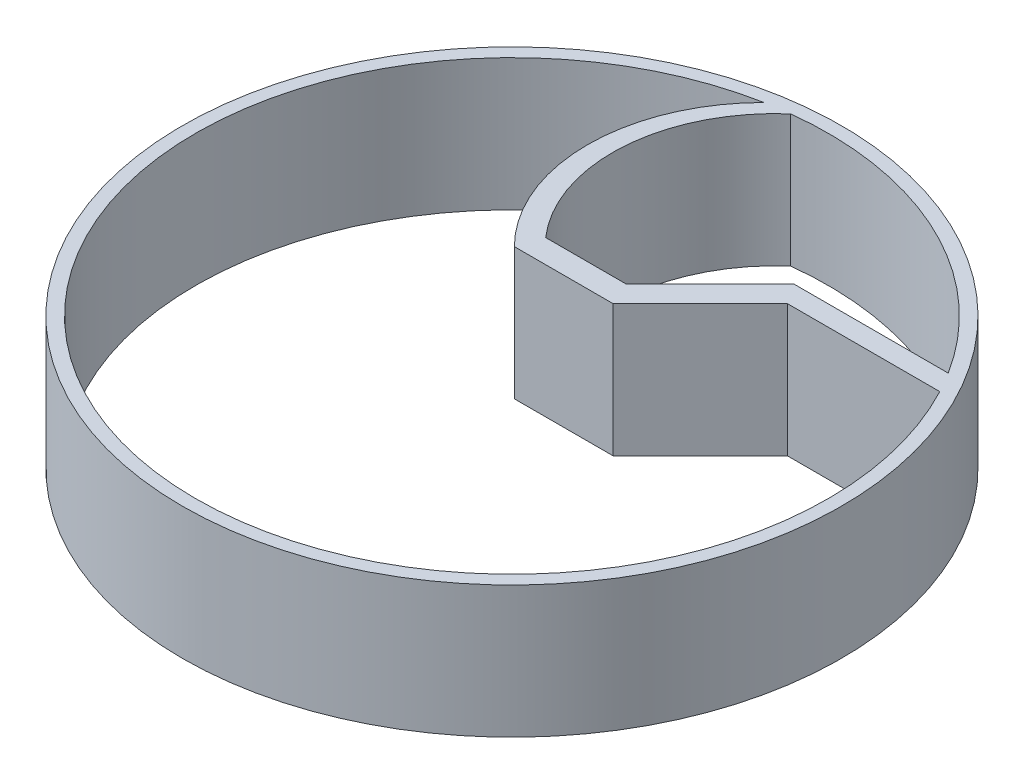
SolidWorks part; units mm, degrees
ref_plane "Front Plane" through (0, 0, 0) normal (0, 0, 1) x (1, 0, 0)
ref_plane "Top Plane" through (0, 0, 0) normal (0, 1, 0) x (1, 0, 0)
ref_plane "Right Plane" through (0, 0, 0) normal (1, 0, 0) x (0, 0, -1)
sketch "Sketch1" plane through (0, 0, 0) normal (0, 1, 0) x (1, 0, 0)
  circle A0 centre (0, 0) radius 2.5
  circle A1 centre (0, 0) radius 2.4
  dimension "D1" = 5
  dimension "D2" = 4.8
extrude "Boss-Extrude1" add sketch "Sketch1" along normal blind 1
sketch "Sketch2" plane through (0, 0, 0) normal (0, 1, 0) x (1, 0, 0)
  line L0 (2.1196, 1.1257) -> (0.9642, 1.1257)
  line L1 (0.9642, 1.1257) -> (0.3029, 0.4644)
  line L2 (0.3029, 0.4644) -> (-0.446, 0.4644)
  line L3 (2.0307, 1.2791) -> (0.8592, 1.2791)
  line L4 (0.8592, 1.2791) -> (0.2229, 0.6428)
  line L5 (0.2229, 0.6428) -> (-0.387, 0.6428)
  circle A0 centre (0, 0) radius 2.4 construction
  arc A1 (-0.446, 0.4644) -> (-0.446, 2.3582) centre (0.5009, 1.4113) cw
  arc A2 (-0.387, 0.6428) -> (-0.2701, 2.3848) centre (0.5424, 1.4554) cw
  arc A3 (-0.446, 2.3582) -> (-0.2701, 2.3848) centre (0, 0) cw
  arc A4 (2.0307, 1.2791) -> (2.1196, 1.1257) centre (0, 0) cw
extrude "Boss-Extrude2" add sketch "Sketch2" along normal blind 1
scale "Scale1" scale about centroid uniform scaling yes scale factor 6
